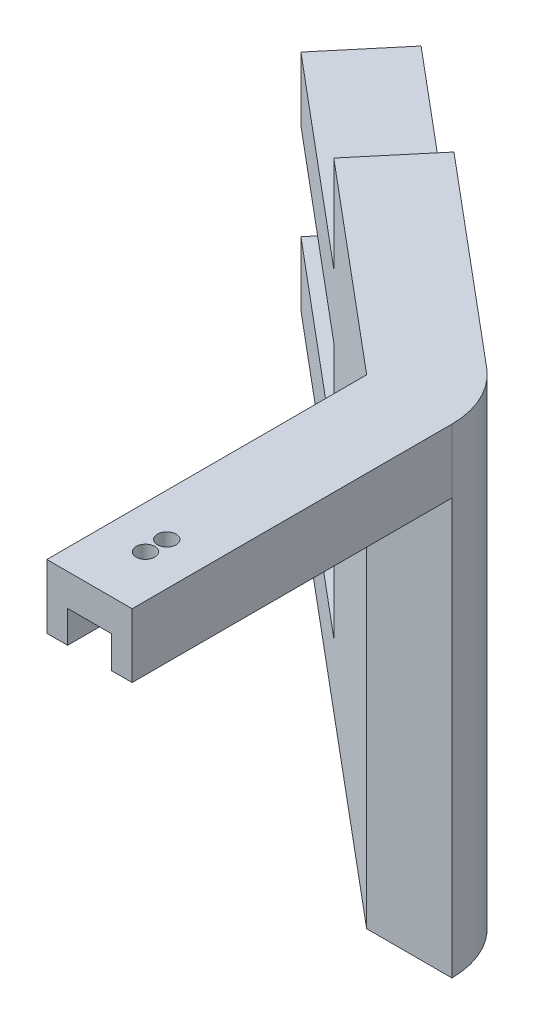
SolidWorks part; units mm, degrees
note: The reader was unsure of these and kept them because the rebuilt part matched: shared geometry of "草图1<4>", "草图2<4>".
ref_plane "前视基准面" through (0, 0, 0) normal (0, 0, 1) x (1, 0, 0)
ref_plane "上视基准面" through (0, 0, 0) normal (0, 1, 0) x (1, 0, 0)
ref_plane "右视基准面" through (0, 0, 0) normal (1, 0, 0) x (0, 0, -1)
other "Configuration Table"
sketch "草图1" plane through (0, 0, 0) normal (0, 1, 0) x (1, 0, 0)
  line L0 (-8, 30) -> (2.2846, 42.2567)
  line L1 (-8, 30) -> (8, 30)
  line L2 (-8, 30) -> (-8, -30)
  line L3 (-8, -30) -> (8, -30)
  line L4 (8, 30) -> (8, -30)
  line L5 (-8, 30) -> (8, -30) construction
  line L6 (-8, -30) -> (8, 30) construction
  line L7 (-8, 30) -> (-84.6044, 94.2788)
  line L8 (2.2846, 42.2567) -> (-74.3198, 106.5355)
  line L9 (-84.6044, 94.2788) -> (-74.3198, 106.5355)
  arc A0 (8, 30) -> (2.2846, 42.2567) centre (-8, 30) ccw
  point P0 (0, 0)
  dimension "D1" = 16
  dimension "D2" = 60
  dimension "D3" = 100
extrude "凸台-拉伸1" add sketch "草图1" against normal blind 12 contours L4 L1 L2 L3
extrude "凸台-拉伸2" add sketch "草图1<4>" against normal blind 90 contours L9 L7 L0 L8 | L1 A0 L0
sketch "草图1<4>" plane through (0, 0, 0) normal (0, 1, 0) x (1, 0, 0) same geometry as "草图1"
sketch "草图2" plane through (0, 0, 0) normal (0, 1, 0) x (1, 0, 0)
  line L0 (0, -30) -> (0, 66.0623) construction
  line L1 (-8, -30) -> (8, -30) construction
  line L2 (0, -30) -> (0, -19.5)
  line L3 (-4.1, -10) -> (4.1, -10)
  line L4 (-4.1, -10) -> (-4.1, -30)
  line L5 (-4.1, -30) -> (4.1, -30)
  line L6 (4.1, -10) -> (4.1, -30)
  line L7 (-4.1, -10) -> (4.1, -30) construction
  line L8 (-4.1, -30) -> (4.1, -10) construction
  line L9 (0, -19.5) -> (0, -15.5)
  circle A0 centre (0, -19.5) radius 1.75
  circle A1 centre (0, -15.5) radius 1.75
  point P5 (0, -20)
  dimension "D1" = 8.2
  dimension "D2" = 20
sketch "草图3" plane through (-96.0712, 0, -80.6133) normal (-0.766, 0, -0.6428) x (-0.6428, 0, 0.766)
  line L0 (-33.839, 0) -> (-17.839, 0)
  line L1 (-33.839, 0) -> (-33.839, -18)
  line L2 (-17.839, 0) -> (-17.839, -18)
  line L3 (-33.839, -18) -> (-17.839, -18)
  line L4 (-33.839, -30) -> (-33.839, -48)
  line L5 (-33.839, -48) -> (-17.839, -48)
  line L6 (-33.839, -30) -> (-17.839, -30)
  line L7 (-17.839, -30) -> (-17.839, -48)
  line L8 (-33.839, -60) -> (-33.839, -78)
  line L9 (-33.839, -78) -> (-17.839, -78)
  line L10 (-33.839, -60) -> (-17.839, -60)
  line L11 (-17.839, -60) -> (-17.839, -78)
  dimension "D1" = 18
  dimension "D2" = 3
extrude "切除-拉伸2" cut sketch "草图3" against normal blind 50 contours L8 L9 L11 L10 | L4 L5 L7 L6 | L0 L1 L3 L2
extrude "切除-拉伸3" cut sketch "草图2" against normal blind 6 from offset 6 offset against normal yes
extrude "切除-拉伸4" cut sketch "草图2<4>" against normal blind 12
sketch "草图2<4>" plane through (0, 0, 0) normal (0, 1, 0) x (1, 0, 0) same geometry as "草图2"
